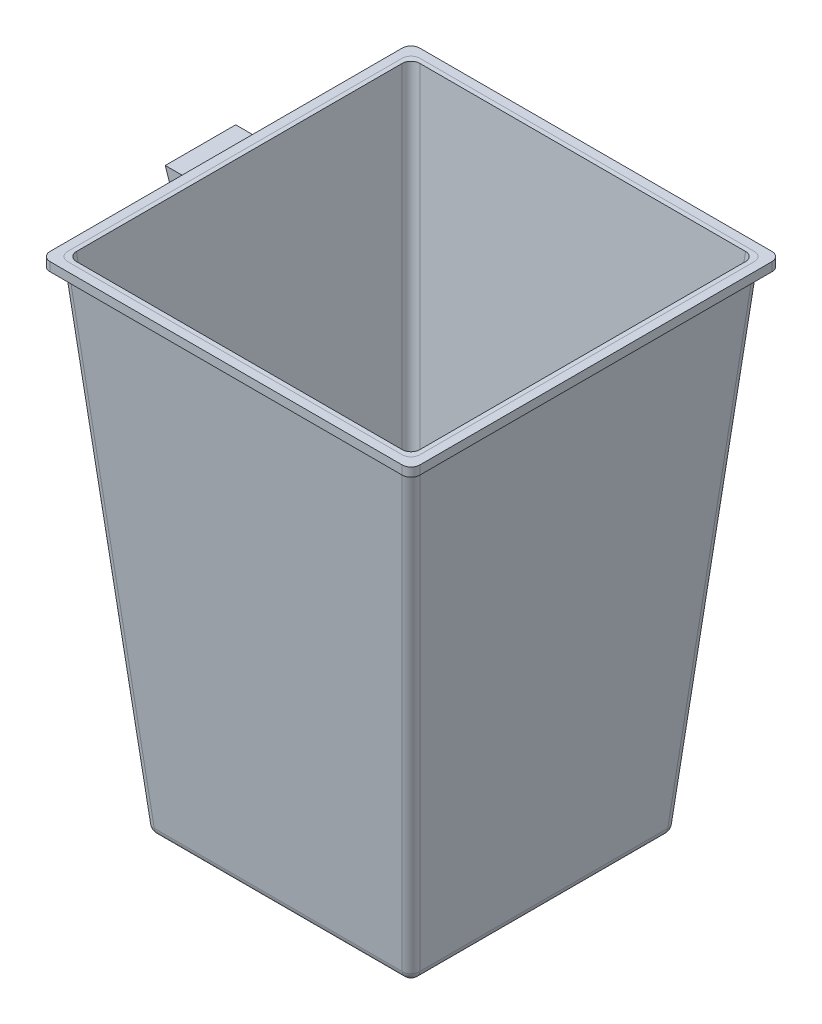
SolidWorks part; units mm, degrees
ref_plane "Front Plane" through (0, 0, 0) normal (0, 0, 1) x (1, 0, 0)
ref_plane "Top Plane" through (0, 0, 0) normal (0, 1, 0) x (1, 0, 0)
ref_plane "Right Plane" through (0, 0, 0) normal (1, 0, 0) x (0, 0, -1)
sketch "Sketch1" plane through (0, 0, 0) normal (0, 0, 1) x (1, 0, 0)
  line L0 (-200, 566.5886) -> (-150, 0)
  line L1 (0, 744.1246) -> (0, -175.4211) construction
  line L2 (-200, 566.5886) -> (200, 566.5886)
  line L3 (-150, 0) -> (150, 0)
  line L4 (200, 566.5886) -> (150, 0)
  point P8 (0, 0)
  point P9 (0, 566.5886)
  dimension "D1" = 150
  dimension "D2" = 200
extrude "Boss-Extrude1" add sketch "Sketch1" along normal blind 200 and the other way blind 200
sketch "Sketch3" plane through (0, 0, 0) normal (1, 0, 0) x (0, 0, -1)
  line L0 (0, 613.0939) -> (0, -105.7235) construction
  line L2 (200, 0) -> (-200, 0) construction
  line L3 (-150, 0) -> (-200, 566.5886)
  line L4 (200, 566.5886) -> (-200, 566.5886) construction
  line L6 (150, 0) -> (200, 566.5886)
  line L7 (-200, 566.5886) -> (-200, 0)
  line L8 (-200, 0) -> (-150, 0)
  line L9 (200, 566.5886) -> (200, 0)
  line L10 (200, 0) -> (150, 0)
  point P12 (0, 0)
  point P13 (0, 566.5886)
  dimension "D1" = 200
  dimension "D2" = 150
extrude "Cut-Extrude2" cut sketch "Sketch3" against normal blind 300 and the other way blind 300
shell "Shell1" thickness 5 removed face at (0, 566.5886, 0)
fillet "Fillet1" radius 10 8 edges at (-175, 283.2943, 175) (-175, 283.2943, -175) (170.2012, 285.7943, -170.2012) (175, 283.2943, 175) (170.2012, 285.7943, 170.2012) (175, 283.2943, -175) (-170.2012, 285.7943, 170.2012) (-170.2012, 285.7943, -170.2012)
fillet "Fillet2" radius 10 8 edges at (142.5089, 5, -142.5089) (0, 5, -145.4218) (-142.5089, 5, -142.5089) (-145.4218, 5, 0) (-142.5089, 5, 142.5089) (0, 5, 145.4218) (142.5089, 5, 142.5089) (145.4218, 5, 0)
fillet "Fillet3" radius 10 8 edges at (-147.0871, 0, -147.0871) (0, 0, -150) (147.0871, 0, -147.0871) (150, 0, 0) (147.0871, 0, 147.0871) (0, 0, 150) (-147.0871, 0, 147.0871) (-150, 0, 0)
sketch "Sketch4" plane through (0, 566.5886, 0) normal (0, 1, 0) x (1, 0, 0)
  line L0 (190.0387, -200) -> (-190.0387, -200) construction
  line L1 (200, 190.0387) -> (200, -190.0387) construction
  line L2 (190.0387, 200) -> (-190.0387, 200) construction
  line L3 (-200, 190.0387) -> (-200, -190.0387) construction
  line L4 (190.0387, -200) -> (-190.0387, -200)
  line L5 (200, 190.0387) -> (200, -190.0387)
  line L6 (190.0387, 200) -> (-190.0387, 200)
  line L7 (-200, 190.0387) -> (-200, -190.0387)
  line L9 (-200, 210) -> (200, 210)
  line L10 (-210, 200) -> (-210, -200)
  line L11 (-200, -210) -> (200, -210)
  line L12 (210, 200) -> (210, -200)
  arc A0 (-200, 210) -> (-210, 200) centre (-200, 200) ccw
  arc A1 (-210, -200) -> (-200, -210) centre (-200, -200) ccw
  arc A2 (200, -210) -> (210, -200) centre (200, -200) ccw
  arc A3 (200, 210) -> (210, 200) centre (200, 200) cw
  ellipse E0 centre (-189.9611, -189.9611) end of major axis (-197.0871, -197.0871) minor radius 10 (-200, -190.0387) -> (-190.0387, -200) ccw construction
  ellipse E1 centre (189.9611, -189.9611) end of major axis (182.8352, -182.8352) minor radius 10 (190.0387, -200) -> (200, -190.0387) ccw construction
  ellipse E2 centre (189.9611, 189.9611) end of major axis (197.0871, 197.0871) minor radius 10 (200, 190.0387) -> (190.0387, 200) ccw construction
  ellipse E3 centre (-189.9611, 189.9611) end of major axis (-182.8352, 182.8352) minor radius 10 (-190.0387, 200) -> (-200, 190.0387) ccw construction
  ellipse E4 centre (-189.9611, -189.9611) end of major axis (-197.0871, -197.0871) minor radius 10 (-200, -190.0387) -> (-190.0387, -200) ccw
  ellipse E5 centre (189.9611, -189.9611) end of major axis (182.8352, -182.8352) minor radius 10 (190.0387, -200) -> (200, -190.0387) ccw
  ellipse E6 centre (189.9611, 189.9611) end of major axis (197.0871, 197.0871) minor radius 10 (200, 190.0387) -> (190.0387, 200) ccw
  ellipse E7 centre (-189.9611, 189.9611) end of major axis (-182.8352, 182.8352) minor radius 10 (-190.0387, 200) -> (-200, 190.0387) ccw
  point P48 (0, 0)
  point P49 (-208.1208, 216.4546)
  dimension "D5" = 10
  dimension "D1" = 10
  dimension "D2" = 10
  dimension "D3" = 10
  dimension "D4" = 10
extrude "Boss-Extrude2" add sketch "Sketch4" against normal blind 10 separate body
ref_plane "Plane1" through (220, 0, 0) normal (1, 0, 0) x (0, 0, -1)
sketch "Sketch6" plane through (0, 0, 0) normal (0, 0, 1) x (1, 0, 0)
  line L0 (-239.1174, 556.5875) -> (-199.1174, 556.5875)
  line L1 (-199.1174, 556.5875) -> (-195.5875, 516.5875)
  line L2 (-150.8049, 9.1209) -> (-200, 566.5886) construction
  line L3 (-195.5875, 516.5875) -> (-225.5875, 516.5875)
  line L4 (-225.5875, 516.5875) -> (-239.1174, 556.5875)
  circle A0 centre (-219.1174, 536.5875) radius 10
  point P3 (0, 0)
  point P8 (0, 0)
  point P9 (-233.8146, 540.91)
  dimension "D4" = 20
  dimension "D1" = 40
  dimension "D2" = 30
  dimension "D3" = 40
  dimension "D5" = 20
  dimension "D6" = 20
extrude "Boss-Extrude3" add sketch "Sketch6" along normal blind 40 and the other way blind 40
